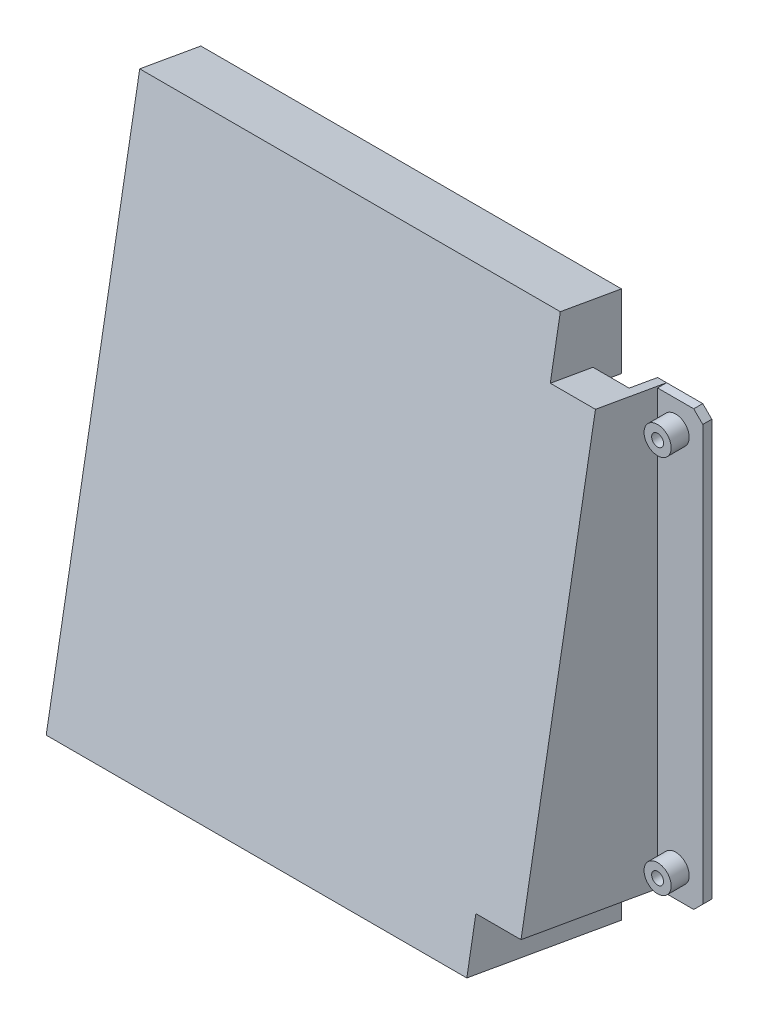
SolidWorks part; units mm, degrees
material "ABS"
ref_plane "Front Plane" through (0, 0, 0) normal (0, 0, 1) x (1, 0, 0)
ref_plane "Top Plane" through (0, 0, 0) normal (0, 1, 0) x (1, 0, 0)
ref_plane "Right Plane" through (0, 0, 0) normal (1, 0, 0) x (0, 0, -1)
sketch "Sketch1" plane through (0, 0, 0) normal (0, 0, 1) x (1, 0, 0)
  line L1 (0, 0) -> (-9.525, 0)
  line L2 (0, 0) -> (0, 76.2)
  line L3 (0, 76.2) -> (-9.525, 76.2)
  line L4 (-9.525, 0) -> (-9.525, 76.2)
  dimension "D1" = 76.2
  dimension "D2" = 9.525
extrude "Boss-Extrude1" add sketch "Sketch1" along normal blind 1.5875
chamfer "Chamfer2" distance 1.5875 angle 45 4 edges at (0, 76.2, 0.7937) (-9.525, 76.2, 0.7937) (0, 0, 0.7937) (-9.525, 0, 0.7937)
hole_wizard "#97 (0.0825) Diameter Hole1" positions "Sketch2" profile "Sketch3" hole size "#97" standard "ANSI Inch" end condition through all
sketch "Sketch2" plane through (0, 0, 1.5875) normal (0, 0, 1) x (1, 0, 0)
  line L0 (-1.5875, 76.2) -> (-7.9375, 76.2) construction
  line L1 (-7.9375, 0) -> (-1.5875, 0) construction
  line L2 (0, 4.7625) -> (-9.525, 4.7625) construction
  line L3 (0, 1.5875) -> (0, 74.6125) construction
  line L4 (-9.525, 74.6125) -> (-9.525, 1.5875) construction
  point P0 (-4.7625, 4.7625)
  point P2 (-4.7625, 71.4375)
  dimension "D1" = 4.7625
  dimension "D2" = 4.7625
sketch "Sketch3" plane through (-4.7625, 4.7625, 1.5875) normal (1, 0, 0) x (0, -1, 0)
  line L0 (0, 0) -> (0, 1.5875)
  line L1 (0, 1.5875) -> (1.0477, 1.5875)
  line L2 (1.0477, 1.5875) -> (1.0477, 0)
  line L5 (1.0477, 0) -> (0, 0)
  line L11 (0, -6.35) -> (0, 107.95) construction
  dimension "Thru Hole Dia." = 2.0955
  dimension "Thru Hole Depth" = 1.5875
ref_plane "Plane1" through (0, 38.1, 0) normal (0, 1, 0) x (1, 0, 0)
sketch "Sketch5" plane through (0, 0, 1.5875) normal (0, 0, 1) x (1, 0, 0)
  line L0 (0.8731, 38.1) -> (-0.8731, 38.1) construction
  circle A0 centre (-4.7625, 4.7625) radius 1.0478
  circle A1 centre (-4.7625, 4.7625) radius 2.3813
  circle A2 centre (-4.7625, 71.4375) radius 2.3813
  circle A3 centre (-4.7625, 71.4375) radius 1.0477
  dimension "D1" = 4.7625
  dimension "D2" = 2.0955
extrude "Boss-Extrude2" add sketch "Sketch5" along normal blind 3.175
ref_plane "Plane2" through (0, 2.2977, 13.031) normal (0, -0.1736, -0.9848) x (-1, 0, 0)
sketch "Sketch7" plane through (0, 2.2977, 13.031) normal (0, -0.1736, -0.9848) x (-1, 0, 0)
  line L1 (9.525, 75.0424) -> (7.9375, 75.0424)
  line L2 (9.525, 75.0424) -> (9.525, -0.2757)
  line L3 (9.525, -0.2757) -> (7.9375, -0.2757)
  line L4 (7.9375, 75.0424) -> (7.9375, -0.2757)
  line L8 (1.5875, 75.0424) -> (7.9375, 75.0424) construction
  line L9 (9.525, 73.479) -> (9.525, 1.5634) construction
extrude "Boss-Extrude4" add sketch "Sketch7" along normal up to surface and the other way blind 12.7 up to face at (-3.7148, 4.7625, 0)
sketch "Sketch9" plane through (-7.9375, 0, 0) normal (1, 0, 0) x (0, 0, -1)
  line L0 (0, 0) -> (-1.5875, 0)
  line L1 (-1.5875, 0) -> (0, -0.2799)
  line L2 (0, -0.2799) -> (0, 0)
extrude "Cut-Extrude1" cut sketch "Sketch9" against normal through all
sketch "Sketch10" plane through (-9.525, 0, 0) normal (-1, 0, 0) x (0, 0, 1)
  line L9 (25.5859, 4.2316) -> (12.5071, 78.4053)
  line L14 (10.4467, 75.4629) -> (22.6434, 6.2919)
  line L18 (7.841, 1.1027) -> (25.5859, 4.2316)
  line L19 (7.841, 1.1027) -> (7.4, 3.6041)
  line L20 (7.4, 3.6041) -> (22.6434, 6.2919)
  line L21 (25.5859, 4.2316) -> (1.5875, 0) construction
  line L22 (12.5071, 78.4053) -> (5.0028, 77.0821)
  line L23 (12.5071, 78.4053) -> (0, 76.2) construction
  line L24 (5.0028, 77.0821) -> (5.4439, 74.5807)
  line L25 (5.4439, 74.5807) -> (10.4467, 75.4629)
  point P3 (10.7725, 76.2865)
  point P19 (23.223, 6.0254)
  dimension "D1" = 6.35
  dimension "D2" = 5.08
  dimension "D3" = 2.54
  dimension "D4" = 2.54
  dimension "D5" = 2.54
extrude "Boss-Extrude5" add sketch "Sketch10" along normal blind 8.89
sketch "Sketch12" plane through (-18.415, 0, 0) normal (-1, 0, 0) x (0, 0, 1)
  line L0 (25.1448, 6.733) -> (27.1737, -4.7735)
  line L1 (25.5859, 4.2316) -> (12.5071, 78.4053) construction
  line L3 (0, 2.2993) -> (0, -9.565)
  line L4 (0, -9.565) -> (27.1737, -4.7735)
  line L6 (0, 76.2) -> (0, 0) construction
  line L7 (22.6434, 6.2919) -> (7.4, 3.6041) construction
  line L8 (25.1448, 6.733) -> (0, 2.2993)
  dimension "D1" = 9.144
extrude "Boss-Extrude7" add sketch "Sketch12" against normal blind 2.54
sketch "Sketch17" plane through (-18.415, 0, 0) normal (-1, 0, 0) x (0, 0, 1)
  line L0 (12.9481, 75.9039) -> (0, 73.6208)
  line L1 (27.1737, -4.7735) -> (12.5071, 78.4053) construction
  line L2 (0, 73.6208) -> (0, 86.5167)
  line L3 (0, 86.5167) -> (10.7428, 88.411)
  line L4 (10.7428, 88.411) -> (12.9481, 75.9039)
  line L5 (0, 76.2) -> (0, 0) construction
  line L6 (5.4439, 74.5807) -> (10.4467, 75.4629) construction
  dimension "D1" = 12.7
extrude "Boss-Extrude11" add sketch "Sketch17" against normal blind 2.54
sketch "Sketch13" plane through (-18.415, 0, 0) normal (-1, 0, 0) x (0, 0, 1)
  line L0 (10.7428, 88.411) -> (0, 86.5167)
  line L3 (8.6824, 85.4685) -> (24.2313, -2.7132)
  line L4 (24.2313, -2.7132) -> (0, -6.9858)
  line L5 (10.7428, 88.411) -> (0, 86.5167) construction
  line L6 (0, -6.9858) -> (0, -9.565)
  line L7 (0, -9.565) -> (27.1737, -4.7735)
  line L8 (27.1737, -4.7735) -> (10.7428, 88.411)
  line L9 (0, 76.2) -> (0, 0) construction
  line L11 (8.6824, 85.4685) -> (0, 83.9376)
  line L12 (0, 86.5167) -> (0, 73.6208) construction
  line L13 (0, 83.9376) -> (0, 86.5167)
  dimension "D1" = 2.54
  dimension "D2" = 2.54
  dimension "D3" = 2.54
extrude "Boss-Extrude8" add sketch "Sketch13" along normal blind 71.374
sketch "Sketch18" plane through (0, 4.062, 23.0366) normal (0, -0.1736, -0.9848) x (-1, 0, 0)
  line L0 (89.789, -6.8797) -> (89.789, 82.6624)
  line L1 (89.789, 82.6624) -> (87.249, 82.6624)
  line L2 (87.249, 82.6624) -> (87.249, -6.8797)
  line L3 (89.789, -6.8797) -> (18.415, -6.8797) construction
  line L4 (87.249, -6.8797) -> (89.789, -6.8797)
  dimension "D1" = 2.54
extrude "Boss-Extrude12" add sketch "Sketch18" along normal up to surface (8.8164 mm away) up to face at (-41.3597, -4.7505, 0)
sketch "Sketch19" plane through (0, -9.2766, 1.6357) normal (0, -0.9848, 0.1736) x (-1, 0, 0)
  line L0 (15.875, 1.6609) -> (15.875, -25.932) construction
  line L1 (28.575, -5.612) -> (77.089, -5.612)
  line L2 (28.575, -5.612) -> (28.575, -18.312)
  line L3 (28.575, -18.312) -> (77.089, -18.312)
  line L4 (77.089, -5.612) -> (77.089, -18.312)
  line L5 (89.789, 1.6609) -> (89.789, -25.932) construction
  line L6 (15.875, -25.932) -> (89.789, -25.932) construction
  dimension "D1" = 12.7
  dimension "D2" = 12.7
  dimension "D3" = 12.7
  dimension "D4" = 7.62
extrude "Cut-Extrude2" cut sketch "Sketch19" against normal up to surface (2.54 mm away) and the other way through all up to face at (-52.832, -4.8495, 12.1156)
equation "\"D4@Sketch10\"=\"D3@Sketch10\""
equation "\"D5@Sketch10\"=\"D3@Sketch10\""
